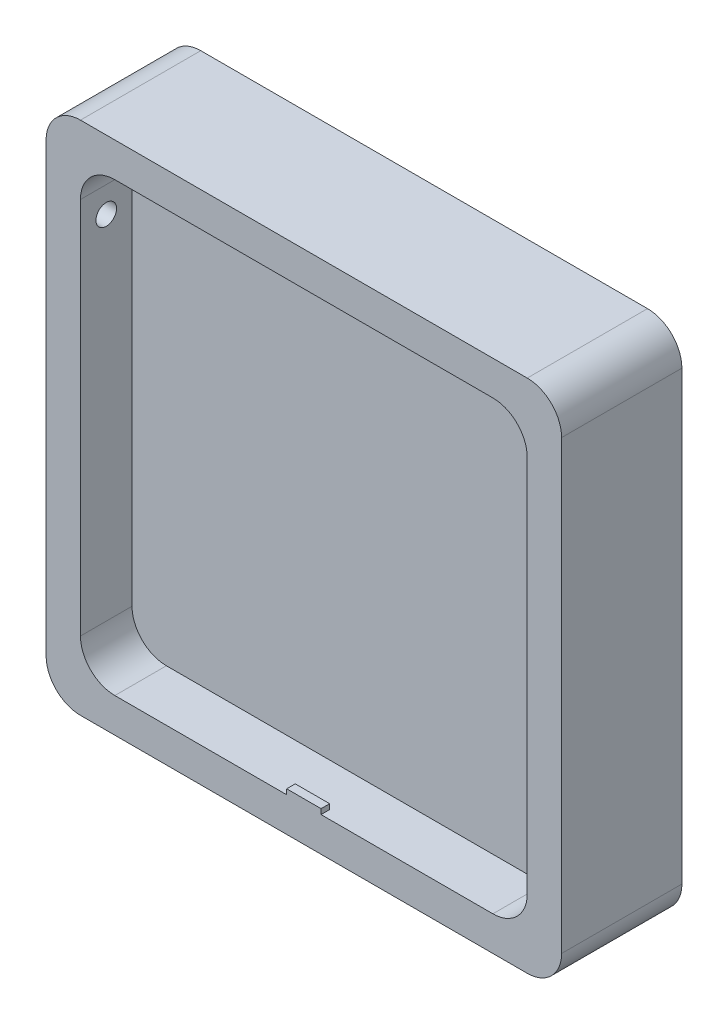
SolidWorks part; units mm, degrees
note: The reader was unsure of these and kept them because the rebuilt part matched: shared geometry of "草图1<7>", "草图9<3>", "草图9<4>", "草图9<5>".
other "标注1"
sketch "草图2" plane through (15, -15, 10) normal (0.3933, -0.7926, 0.466) x (0.9059, 0.4207, -0.0491)
ref_plane "前视基准面" through (0, 0, 0) normal (0, 0, 1) x (1, 0, 0)
ref_plane "上视基准面" through (0, 0, 0) normal (0, 1, 0) x (1, 0, 0)
ref_plane "右视基准面" through (0, 0, 0) normal (1, 0, 0) x (0, 0, -1)
sketch "草图1" plane through (0, 0, 0) normal (0, 0, 1) x (1, 0, 0)
  line L0 (-13, 15) -> (13, 15)
  line L1 (-11, 13) -> (11, 13)
  line L2 (-13, 11) -> (-13, -11)
  line L3 (-11, -13) -> (11, -13)
  line L4 (13, 11) -> (13, -11)
  line L5 (0, -13) -> (0, 13) construction
  line L6 (-13, 0) -> (13, 0) construction
  line L7 (15, 13) -> (15, -13)
  line L8 (-13, -15) -> (13, -15)
  line L9 (-15, 13) -> (-15, -13)
  line L10 (-13, -13) -> (13, -13) construction
  line L11 (-2.25, 0.75) -> (2.25, 0.75)
  line L12 (-2.25, 0.75) -> (-2.25, -0.75)
  line L13 (-2.25, -0.75) -> (2.25, -0.75)
  line L14 (2.25, 0.75) -> (2.25, -0.75)
  line L15 (0, -0.75) -> (0, 0.75) construction
  line L16 (-2.25, 0) -> (2.25, 0) construction
  line L17 (-0.75, 2.25) -> (0.75, 2.25)
  line L18 (-0.75, 2.25) -> (-0.75, -2.25)
  line L19 (-0.75, -2.25) -> (0.75, -2.25)
  line L20 (0.75, 2.25) -> (0.75, -2.25)
  line L21 (0, -2.25) -> (0, 2.25) construction
  line L22 (-0.75, 0) -> (0.75, 0) construction
  line L23 (13, 13) -> (13, -13) construction
  line L24 (-13, 13) -> (13, 13) construction
  line L25 (-13, 13) -> (-13, -13) construction
  line L26 (-15, 15) -> (-15, -15) construction
  line L27 (-15, -15) -> (15, -15) construction
  line L28 (15, 15) -> (15, -15) construction
  line L29 (-15, 15) -> (15, 15) construction
  line L36 (-13, 0) -> (-2.5, 0) construction
  circle A0 centre (0, 0) radius 2.95
  arc A1 (11, -13) -> (13, -11) centre (11, -11) ccw
  arc A2 (13, 11) -> (11, 13) centre (11, 11) ccw
  arc A3 (-13, 11) -> (-11, 13) centre (-11, 11) cw
  arc A4 (-13, -11) -> (-11, -13) centre (-11, -11) ccw
  arc A5 (-15, -13) -> (-13, -15) centre (-13, -13) ccw
  arc A6 (13, -15) -> (15, -13) centre (13, -13) ccw
  arc A7 (15, 13) -> (13, 15) centre (13, 13) ccw
  arc A8 (-15, 13) -> (-13, 15) centre (-13, 13) cw
  point P0 (0, 0)
  point P19 (13, -13)
  point P66 (0.0162, 0.0162)
  dimension "D4" = 5.9
  dimension "D9" = 2
  dimension "D1" = 30
  dimension "D2" = 30
  dimension "D5" = 4.5
  dimension "D6" = 1.5
  dimension "D7" = 4.5
  dimension "D8" = 1.5
  dimension "D3" = 2
extrude "凸台-拉伸1" add sketch "草图1" along normal blind 5 contours A8 L9 A5 L8 A6 L7 A7 L0 A4 L2 A3 L1 A2 L4 A1 L3
extrude "凸台-拉伸3" add sketch "草图1<7>" against normal blind 2 contours L8 A6 L7 A7 L0 A8 L9 A5
sketch "草图1<7>" plane through (0, 0, 0) normal (0, 0, 1) x (1, 0, 0) same geometry as "草图1"
sketch "草图3" plane through (0, 0, 0) normal (0, 0, 1) x (1, 0, 0)
  line L4 (-13, 11) -> (-13, -11)
  line L14 (-13, 11) -> (-13, -11)
  line L18 (-11, -13) -> (11, -13)
  line L20 (-11, -13) -> (11, -13)
  line L36 (13, -11) -> (13, 11)
  line L38 (13, -11) -> (13, 11)
  line L40 (11, 13) -> (-11, 13)
  line L42 (11, 13) -> (-11, 13)
  arc A4 (-13, -11) -> (-11, -13) centre (-11, -11) ccw
  arc A12 (-13, -11) -> (-11, -13) centre (-11, -11) ccw
  arc A14 (11, -13) -> (13, -11) centre (11, -11) ccw
  arc A16 (11, -13) -> (13, -11) centre (11, -11) ccw
  arc A18 (13, 11) -> (11, 13) centre (11, 11) ccw
  arc A19 (13, 11) -> (11, 13) centre (11, 11) ccw
  arc A20 (-11, 13) -> (-13, 11) centre (-11, 11) ccw
  arc A21 (-11, 13) -> (-13, 11) centre (-11, 11) ccw
  dimension "D1" = 0
extrude "凸台-拉伸4" add sketch "草图3" along normal blind 1
sketch "草图9" plane through (0, 0, -2) normal (0, 0, -1) x (-1, 0, 0)
  line L0 (33.361, 130.4306) -> (221.361, 130.4306) construction
  line L1 (-12.6815, 2.8632) -> (-9.8881, 2.2841)
  line L2 (-10.0281, 1.5583) -> (-12.8365, 2.0593)
  line L3 (-11.0348, 6.8739) -> (-8.6908, 5.2402)
  line L4 (-8.2951, 5.8465) -> (-10.6265, 7.4897)
  line L5 (-7.5892, 10.5556) -> (-5.9875, 8.1939)
  line L6 (-5.3439, 8.6275) -> (-6.9413, 10.9925)
  line L7 (-2.9715, 12.6565) -> (-2.4162, 9.8566)
  line L8 (-2.1422, 12.823) -> (-1.6722, 10.0097)
  line L9 (2.1085, 12.8285) -> (1.5965, 10.0221)
  line L10 (2.928, 12.6666) -> (2.3261, 9.8782)
  line L11 (6.9094, 11.0126) -> (5.3439, 8.6275)
  line L12 (7.5892, 10.5556) -> (5.9242, 8.2398)
  line L13 (10.5816, 7.553) -> (8.2601, 5.8959)
  line L14 (8.6723, 5.2708) -> (11.0459, 6.856)
  line L15 (9.872, 2.3526) -> (12.6515, 2.9927)
  line L16 (12.8477, 1.9884) -> (10.029, 1.5521)
  line L17 (10.0163, -1.6324) -> (12.8168, -2.1785)
  line L18 (9.8447, -2.4641) -> (12.6515, -2.9927)
  line L19 (10.9861, -6.9515) -> (8.6342, -5.3331)
  line L20 (8.1666, -6.0247) -> (10.4913, -7.6779)
  line L21 (5.9242, -8.2398) -> (7.5194, -10.6055)
  line L22 (6.7814, -11.0919) -> (5.2544, -8.6823)
  line L23 (2.3261, -9.8782) -> (2.856, -12.6831)
  line L24 (2.0336, -12.8406) -> (1.5401, -10.0309)
  line L25 (-1.5984, -10.0218) -> (-2.1099, -12.8283)
  line L26 (-2.9715, -12.6565) -> (-2.3662, -9.8687)
  line L27 (-10.0163, -1.6324) -> (-12.8168, -2.1785)
  line L28 (-9.8447, -2.4641) -> (-12.6515, -2.9927)
  line L29 (-8.6908, -5.2402) -> (-11.0061, -6.9197)
  line L30 (-8.1666, -6.0247) -> (-10.5636, -7.5781)
  line L31 (-5.9242, -8.2398) -> (-7.5892, -10.5556)
  line L32 (-6.6864, -11.1494) -> (-5.2195, -8.7033)
  line L33 (-4.5064, -2.8659) -> (4.3542, -2.8659) construction
  line L34 (-0.7737, -2.7436) -> (0.7655, -2.7436)
  line L35 (0.7655, -2.7436) -> (0.8783, -3.1233)
  line L36 (0.8783, -3.1233) -> (0.3448, -3.7184)
  line L37 (0.3448, -3.7184) -> (0.3448, -4.3751)
  line L38 (0.3448, -4.3751) -> (1.2169, -5.3331)
  line L39 (1.2169, -5.3331) -> (1.2169, -5.6782)
  line L40 (1.2169, -5.6782) -> (1.0113, -5.8654)
  line L41 (1.0113, -5.8654) -> (0.7809, -5.7718)
  line L42 (0.7809, -5.7718) -> (-0.071, -5.0081)
  line L43 (-0.071, -5.0081) -> (-0.9099, -5.7718)
  line L44 (-0.9099, -5.7718) -> (-1.1895, -5.7718)
  line L45 (-1.1895, -5.7718) -> (-1.3252, -5.6227)
  line L46 (-1.3252, -5.6227) -> (-1.3252, -5.3331)
  line L47 (-1.3252, -5.3331) -> (-0.4269, -4.5154)
  line L48 (-0.4269, -4.5154) -> (-0.3895, -3.7184)
  line L49 (-0.3895, -3.7184) -> (-0.8761, -3.2822)
  line L50 (-0.8761, -3.2822) -> (-0.8761, -2.9334)
  line L51 (-0.8761, -2.9334) -> (-0.7737, -2.7436)
  circle A0 centre (0, 0) radius 9.3261
  circle A1 centre (0, 0) radius 10.1484
  circle A2 centre (0, 0) radius 13.0007
  circle A3 centre (0, 0) radius 13.7989
  circle A4 centre (-4.5064, -2.8659) radius 1.0431
  circle A5 centre (4.3542, -2.8659) radius 0.9871
extrude "切除-拉伸2" cut sketch "草图9" against normal blind 0.6 contours A1 A0 | L31 A2 L32 A1 | A3 A2 | L26 A2 L25 A1 | L24 A2 L23 A1 | L22 A2 L21 A1 | L20 A2 L19 A1 | L18 A2 L17 A1 | L16 A2 L15 A1 | L14 A2 L13 A1 | L12 A2 L11 A1 | L10 A2 L9 A1 | L8 A2 L7 A1 | L6 A2 L5 A1 | L1 A2 L2 A1 | L27 A2 L28 A1 | L29 A2 L30 A1 | L4 A2 L3 A1 | L51 L34 L35 L36 L37 L38 L39 L40 L41 L42 L43 L44 L45 L46 L47 L48 L49 L50
extrude "凸台-拉伸7" add sketch "草图9<3>" against normal blind 0.6 separate body contours A3 A2 | L6 A2 L5 A1 | A1 A0 | L8 A2 L7 A1 | L10 A2 L9 A1 | L12 A2 L11 A1 | L14 A2 L13 A1 | L16 A2 L15 A1 | L18 A2 L17 A1 | L20 A2 L19 A1 | L22 A2 L21 A1 | L24 A2 L23 A1 | L26 A2 L25 A1 | L31 A2 L32 A1 | L29 A2 L30 A1 | L27 A2 L28 A1 | L1 A2 L2 A1 | L4 A2 L3 A1 | L51 L50 L49 L48 L47 L46 L45 L44 L43 L42 L41 L40 L39 L38 L37 L36 L35 L34
sketch "草图9<3>" plane through (0, 0, -2) normal (0, 0, -1) x (-1, 0, 0) same geometry as "草图9"
extrude "切除-拉伸3" cut sketch "草图9<4>" against normal through all contours L7 A2 L6 A1 | L11 A2 L10 A1 | L15 A2 L14 A1 | L19 A2 L18 A1 | L23 A2 L22 A1 | L32 A2 L26 A1 | L28 A2 L29 A1 | L3 A2 L1 A1 | A4 | A5
sketch "草图9<4>" plane through (0, 0, -2) normal (0, 0, -1) x (-1, 0, 0) same geometry as "草图9"
extrude "凸台-拉伸8" add sketch "草图9<5>" against normal blind 0.6 separate body contours L3 A2 L1 A1 | L7 A2 L6 A1 | L11 A2 L10 A1 | L15 A2 L14 A1 | L19 A2 L18 A1 | L23 A2 L22 A1 | L32 A2 L26 A1 | L28 A2 L29 A1 | A4 | A5
sketch "草图9<5>" plane through (0, 0, -2) normal (0, 0, -1) x (-1, 0, 0) same geometry as "草图9"
sketch "草图10" plane through (0, 0, 1) normal (0, 0, 1) x (1, 0, 0)
  line L0 (11.0061, -6.9197) -> (8.6908, -5.2402) construction
  line L1 (12.6515, -2.9927) -> (9.8447, -2.4641) construction
  line L2 (5.2195, -8.7033) -> (6.6864, -11.1494) construction
  line L3 (2.3662, -9.8687) -> (2.9715, -12.6565) construction
  line L4 (-2.856, -12.6831) -> (-2.3261, -9.8782) construction
  line L5 (-5.2544, -8.6823) -> (-6.7814, -11.0919) construction
  line L6 (-8.6342, -5.3331) -> (-10.9861, -6.9515) construction
  line L7 (-12.6515, -2.9927) -> (-9.8447, -2.4641) construction
  line L8 (-12.6515, 2.9927) -> (-9.872, 2.3526) construction
  line L9 (-11.0459, 6.856) -> (-8.6723, 5.2708) construction
  line L10 (9.8881, 2.2841) -> (12.6815, 2.8632) construction
  line L11 (8.6908, 5.2402) -> (11.0348, 6.8739) construction
  line L12 (6.9413, 10.9925) -> (5.3439, 8.6275) construction
  line L13 (2.4162, 9.8566) -> (2.9715, 12.6565) construction
  line L14 (-5.3439, 8.6275) -> (-6.9094, 11.0126) construction
  line L15 (-2.3261, 9.8782) -> (-2.928, 12.6666) construction
  line L16 (11.0061, -6.9197) -> (8.6908, -5.2402)
  line L17 (12.6515, -2.9927) -> (9.8447, -2.4641)
  line L18 (5.2195, -8.7033) -> (6.6864, -11.1494)
  line L19 (2.3662, -9.8687) -> (2.9715, -12.6565)
  line L20 (-2.856, -12.6831) -> (-2.3261, -9.8782)
  line L21 (-5.2544, -8.6823) -> (-6.7814, -11.0919)
  line L22 (-8.6342, -5.3331) -> (-10.9861, -6.9515)
  line L23 (-12.6515, -2.9927) -> (-9.8447, -2.4641)
  line L24 (-12.6515, 2.9927) -> (-9.872, 2.3526)
  line L25 (-11.0459, 6.856) -> (-8.6723, 5.2708)
  line L26 (9.8881, 2.2841) -> (12.6815, 2.8632)
  line L27 (8.6908, 5.2402) -> (11.0348, 6.8739)
  line L28 (6.9413, 10.9925) -> (5.3439, 8.6275)
  line L29 (2.4162, 9.8566) -> (2.9715, 12.6565)
  line L30 (-5.3439, 8.6275) -> (-6.9094, 11.0126)
  line L31 (-2.3261, 9.8782) -> (-2.928, 12.6666)
  line L36 (-13, 11) -> (-13, -11)
  line L37 (-13, 11) -> (-13, -11)
  line L38 (-11, -13) -> (11, -13)
  line L39 (-11, -13) -> (11, -13)
  line L44 (13, -11) -> (13, 11)
  line L45 (13, -11) -> (13, 11)
  line L46 (11, 13) -> (-11, 13)
  line L47 (11, 13) -> (-11, 13)
  arc A9 (11.0061, -6.9197) -> (12.6515, -2.9927) centre (0, 0) ccw construction
  arc A11 (8.6908, -5.2402) -> (9.8447, -2.4641) centre (0, 0) ccw construction
  arc A12 (2.9715, -12.6565) -> (6.6864, -11.1494) centre (0, 0) ccw construction
  arc A13 (2.3662, -9.8687) -> (5.2195, -8.7033) centre (0, 0) ccw construction
  arc A14 (-6.7814, -11.0919) -> (-2.856, -12.6831) centre (0, 0) ccw construction
  arc A15 (-5.2544, -8.6823) -> (-2.3261, -9.8782) centre (0, 0) ccw construction
  arc A16 (-12.6515, -2.9927) -> (-10.9861, -6.9515) centre (0, 0) ccw construction
  arc A17 (-9.8447, -2.4641) -> (-8.6342, -5.3331) centre (0, 0) ccw construction
  arc A18 (-11.0459, 6.856) -> (-12.6515, 2.9927) centre (0, 0) ccw construction
  arc A19 (9.8881, 2.2841) -> (8.6908, 5.2402) centre (0, 0) ccw construction
  arc A20 (12.6815, 2.8632) -> (11.0348, 6.8739) centre (0, 0) ccw construction
  arc A21 (5.3439, 8.6275) -> (2.4162, 9.8566) centre (0, 0) ccw construction
  arc A22 (6.9413, 10.9925) -> (2.9715, 12.6565) centre (0, 0) ccw construction
  arc A23 (-2.3261, 9.8782) -> (-5.3439, 8.6275) centre (0, 0) ccw construction
  arc A24 (-2.928, 12.6666) -> (-6.9094, 11.0126) centre (0, 0) ccw construction
  arc A25 (11.0061, -6.9197) -> (12.6515, -2.9927) centre (0, 0) ccw
  arc A26 (8.6908, -5.2402) -> (9.8447, -2.4641) centre (0, 0) ccw
  arc A27 (2.9715, -12.6565) -> (6.6864, -11.1494) centre (0, 0) ccw
  arc A28 (2.3662, -9.8687) -> (5.2195, -8.7033) centre (0, 0) ccw
  arc A29 (-6.7814, -11.0919) -> (-2.856, -12.6831) centre (0, 0) ccw
  arc A30 (-5.2544, -8.6823) -> (-2.3261, -9.8782) centre (0, 0) ccw
  arc A31 (-12.6515, -2.9927) -> (-10.9861, -6.9515) centre (0, 0) ccw
  arc A32 (-9.8447, -2.4641) -> (-8.6342, -5.3331) centre (0, 0) ccw
  arc A33 (-11.0459, 6.856) -> (-12.6515, 2.9927) centre (0, 0) ccw
  arc A34 (9.8881, 2.2841) -> (8.6908, 5.2402) centre (0, 0) ccw
  arc A35 (12.6815, 2.8632) -> (11.0348, 6.8739) centre (0, 0) ccw
  arc A36 (5.3439, 8.6275) -> (2.4162, 9.8566) centre (0, 0) ccw
  arc A37 (6.9413, 10.9925) -> (2.9715, 12.6565) centre (0, 0) ccw
  arc A38 (-2.3261, 9.8782) -> (-5.3439, 8.6275) centre (0, 0) ccw
  arc A39 (-2.928, 12.6666) -> (-6.9094, 11.0126) centre (0, 0) ccw
  circle A40 centre (4.5064, -2.8659) radius 1.0431 construction
  circle A41 centre (-4.3542, -2.8659) radius 0.9871 construction
  circle A42 centre (4.5064, -2.8659) radius 1.0431
  circle A43 centre (-4.3542, -2.8659) radius 0.9871
  arc A44 (-8.6723, 5.2708) -> (-9.872, 2.3526) centre (0, 0) ccw construction
  arc A45 (-8.6723, 5.2708) -> (-9.872, 2.3526) centre (0, 0) ccw
  arc A46 (-11, 13) -> (-13, 11) centre (-11, 11) ccw
  arc A47 (-11, 13) -> (-13, 11) centre (-11, 11) ccw
  arc A48 (-13, -11) -> (-11, -13) centre (-11, -11) ccw
  arc A49 (-13, -11) -> (-11, -13) centre (-11, -11) ccw
  arc A54 (11, -13) -> (13, -11) centre (11, -11) ccw
  arc A55 (11, -13) -> (13, -11) centre (11, -11) ccw
  arc A56 (13, 11) -> (11, 13) centre (11, 11) ccw
  arc A57 (13, 11) -> (11, 13) centre (11, 11) ccw
  dimension "D1" = 0
extrude "凸台-拉伸9" add sketch "草图10" along normal blind 0.6 separate body
sketch "草图11" plane through (0, 0, 1.6) normal (0, 0, 1) x (1, 0, 0)
  line L4 (11, 13) -> (-11, 13)
  line L5 (-13, 11) -> (-13, -11)
  line L6 (-11, -13) -> (11, -13)
  line L7 (13, -11) -> (13, 11)
  line L8 (11, 13) -> (-11, 13)
  line L9 (-13, 11) -> (-13, -11)
  line L10 (-11, -13) -> (11, -13)
  line L11 (13, -11) -> (13, 11)
  arc A5 (-11, 13) -> (-13, 11) centre (-11, 11) ccw
  arc A6 (-13, -11) -> (-11, -13) centre (-11, -11) ccw
  arc A7 (11, -13) -> (13, -11) centre (11, -11) ccw
  arc A8 (13, 11) -> (11, 13) centre (11, 11) ccw
  arc A9 (-11, 13) -> (-13, 11) centre (-11, 11) ccw
  arc A10 (-13, -11) -> (-11, -13) centre (-11, -11) ccw
  arc A11 (11, -13) -> (13, -11) centre (11, -11) ccw
  arc A12 (13, 11) -> (11, 13) centre (11, 11) ccw
  dimension "D1" = 0
extrude "凸台-拉伸11" add sketch "草图11" along normal blind 0.4 separate body
ref_plane "基准面1" through (0, 0, 0) normal (1, 0, 0) x (0, 0, -1)
sketch "草图12" plane through (-13, 0, 0) normal (1, 0, 0) x (0, 0, -1)
  line L0 (-5, 11) -> (-1, 11) construction
  line L1 (-5, 11) -> (-5, -11) construction
  circle A0 centre (-3.5, 9.5) radius 0.6
  dimension "D1" = 1.2
  dimension "D2" = 1.5
  dimension "D3" = 1.5
extrude "切除-拉伸4" cut sketch "草图12" against normal blind 1.2
mirror "镜向1" about plane through (0, 0, 0) normal (1, 0, 0) of "切除-拉伸4"
sketch "草图13" plane through (0, -13, 0) normal (0, 1, 0) x (1, 0, 0)
  line L0 (-11, -5) -> (11, -5) construction
  line L1 (-1, -5) -> (1, -5)
  line L2 (-1, -5) -> (-1, -4.5)
  line L3 (-1, -4.5) -> (1, -4.5)
  line L4 (1, -5) -> (1, -4.5)
  line L5 (-1, -5) -> (1, -4.5) construction
  line L6 (-1, -4.5) -> (1, -5) construction
  point P0 (0, -4.75)
  point P7 (2.4452, -5)
  point P8 (0, -5)
  point P9 (0, -5)
  dimension "D1" = 0.5
  dimension "D2" = 2
extrude "凸台-拉伸12" add sketch "草图13" along normal blind 0.3
